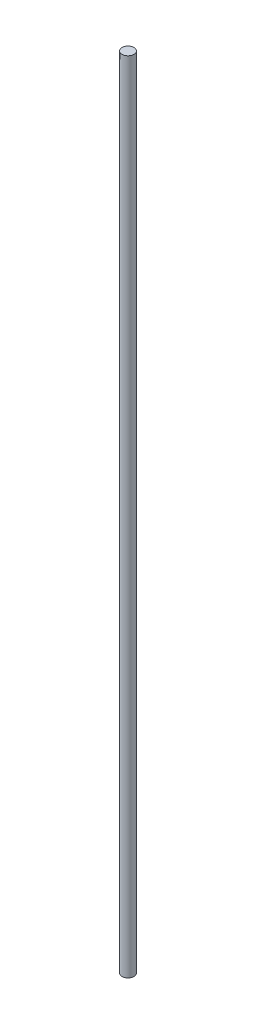
SolidWorks part; units mm, degrees
ref_plane "Front Plane" through (0, 0, 0) normal (0, 0, 1) x (1, 0, 0)
ref_plane "Top Plane" through (0, 0, 0) normal (0, 1, 0) x (1, 0, 0)
ref_plane "Right Plane" through (0, 0, 0) normal (1, 0, 0) x (0, 0, -1)
sketch "Sketch1" plane through (0, 0, 0) normal (0, 1, 0) x (1, 0, 0)
  circle A0 centre (0, 0) radius 1.5
  dimension "D1" = 3
extrude "Boss-Extrude1" add sketch "Sketch1" along normal blind 200
ref_axis "CENTER" [suppressed] through (0, 300, 0) along (0, -1, 0)
ref_plane "MIDPLANE" [suppressed] through (0, 100, 0) normal (0, 1, 0) x (1, 0, 0)
equation "\"LENGTH\" = 200mm"
equation "\"ROD_DIA\"=3"
equation "\"D1@Sketch1\"=\"ROD_DIA\""
equation "\"D1@Boss-Extrude1\"=\"LENGTH\""
